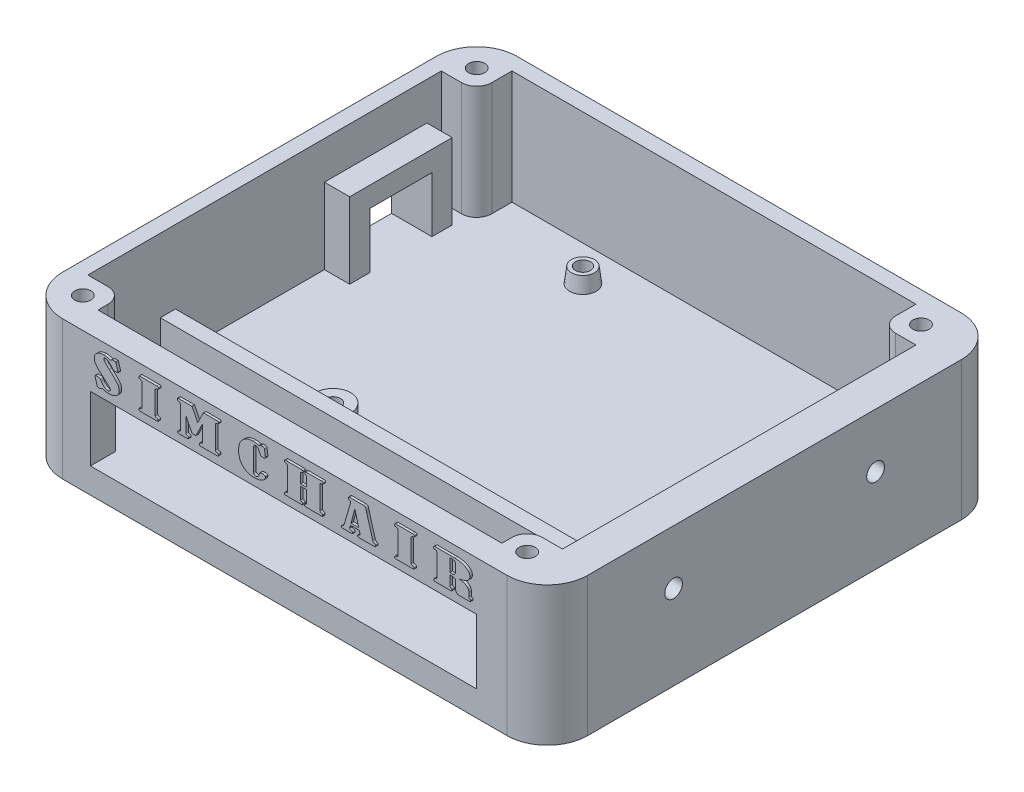
SolidWorks part; units mm, degrees
ref_plane "Спереди" through (0, 0, 0) normal (0, 0, 1) x (1, 0, 0)
ref_plane "Сверху" through (0, 0, 0) normal (0, 1, 0) x (1, 0, 0)
ref_plane "Справа" through (0, 0, 0) normal (1, 0, 0) x (0, 0, -1)
sketch "Sketch1" plane through (0, 0, 0) normal (0, 1, 0) x (1, 0, 0)
  line L1 (50, 45) -> (-50, 45)
  line L2 (50, 45) -> (50, -45)
  line L3 (50, -45) -> (-50, -45)
  line L4 (-50, 45) -> (-50, -45)
  line L5 (50, 45) -> (-50, -45) construction
  line L6 (50, -45) -> (-50, 45) construction
  point P0 (0, 0)
  dimension "D1" = 100
  dimension "D2" = 90
extrude "Boss-Extrude1" add sketch "Sketch1" along normal blind 5
sketch "Sketch2" plane through (0, 5, 0) normal (0, 1, 0) x (1, 0, 0)
  line L1 (-50, 45) -> (50, 45)
  line L2 (-50, 45) -> (-50, -45)
  line L3 (-50, -45) -> (50, -45)
  line L4 (50, 45) -> (50, -45)
  line L5 (-50, 45) -> (50, -45) construction
  line L6 (-50, -45) -> (50, 45) construction
  line L7 (-47, 42) -> (47, 42)
  line L8 (-47, 42) -> (-47, -42)
  line L9 (-47, -42) -> (47, -42)
  line L10 (47, 42) -> (47, -42)
  line L11 (-47, 42) -> (47, -42) construction
  line L12 (-47, -42) -> (47, 42) construction
  point P0 (0, 0)
  point P7 (0, 0)
  dimension "D1" = 3
  dimension "D2" = 3
  dimension "D3" = 94
  dimension "D4" = 84
  dimension "D5" = 100
  dimension "D6" = 90
extrude "Boss-Extrude2" add sketch "Sketch2" along normal blind 22.5
sketch "Эскиз1" plane through (0, 5, 0) normal (0, 1, 0) x (1, 0, 0)
  line L0 (-34.3, 37.65) -> (34.3, 37.65) construction
  line L1 (34.3, -15.65) -> (-34.3, 37.65) construction
  line L2 (-34.3, -15.65) -> (34.3, 37.65) construction
  line L3 (0, 42) -> (0, -42) construction
  line L4 (-47, -42) -> (47, -42) construction
  line L5 (31.8, -13.15) -> (-34.3, -13.15) construction
  line L6 (47, 42) -> (-47, 42) construction
  line L7 (34.3, 37.65) -> (34.3, -15.65) construction
  line L8 (34.3, -15.65) -> (-34.3, -15.65) construction
  line L9 (-34.3, -15.65) -> (-34.3, 37.65) construction
  line L10 (-34.3, 37.65) -> (-20.3, 37.65) construction
  line L11 (31.8, 37.65) -> (31.8, 19.85) construction
  line L12 (31.8, 19.85) -> (31.8, 35.05) construction
  line L13 (-20.3, 37.65) -> (-19, 37.65) construction
  line L14 (-20.3, 37.65) -> (-20.3, -15.65) construction
  line L15 (-19, 37.65) -> (31.8, 37.65) construction
  line L16 (31.8, 37.65) -> (31.8, -15.65) construction
  line L17 (31.8, -15.65) -> (31.8, -13.15) construction
  line L18 (31.8, 35.05) -> (-19, 35.05) construction
  line L19 (-19, 37.65) -> (-19, -15.65) construction
  circle A0 centre (31.8, -8.05) radius 1.5
  circle A1 centre (-20.3, -13.15) radius 1.5
  circle A2 centre (31.8, 19.85) radius 1.5
  circle A3 centre (-19, 35.05) radius 1.5
  circle A4 centre (-20.3, -13.15) radius 3.5
  circle A5 centre (-19, 35.05) radius 3.5
  circle A6 centre (31.8, 19.85) radius 3.5
  circle A7 centre (31.8, -8.05) radius 3.5
  point P3 (0, 11)
  point P11 (-20.3, -13.15)
  point P34 (0, 0)
  dimension "D12" = 3
  dimension "D2" = 7
  dimension "D3" = 53.3
  dimension "D4" = 68.6
  dimension "D5" = 14
  dimension "D6" = 1.3
  dimension "D7" = 50.8
  dimension "D8" = 2.5
  dimension "D9" = 5.1
  dimension "D10" = 27.9
  dimension "D11" = 15.2
  dimension "D13" = 31
extrude "Boss-Extrude3" add sketch "Эскиз1" along normal blind 3
sketch "Sketch7" plane through (0, 0, 0) normal (0, -1, 0) x (1, 0, 0)
  line L0 (-50, -45) -> (-50, 45) construction
  line L1 (-44, 39) -> (44, -39) construction
  line L2 (44, -39) -> (-44, -39) construction
  line L3 (-44, -39) -> (-44, 39) construction
  line L4 (-44, 39) -> (44, 39) construction
  line L5 (44, 39) -> (44, -39) construction
  line L6 (-50, 45) -> (50, 45) construction
  line L8 (50, 45) -> (50, -45) construction
  line L9 (50, -45) -> (-50, -45) construction
  circle A0 centre (44, -39) radius 1.6
  circle A1 centre (-44, -39) radius 1.6
  circle A2 centre (-44, 39) radius 1.6
  circle A3 centre (44, 39) radius 1.6
  dimension "D2" = 3.2
  dimension "D3" = 6
  dimension "D1" = 6
  dimension "D4" = 6
  dimension "D5" = 6
extrude "Cut-Extrude3" cut sketch "Sketch7" against normal through all
sketch "Sketch8" plane through (0, 0, 0) normal (0, -1, 0) x (1, 0, 0)
  line L0 (-50, 45) -> (50, 45) construction
  line L1 (42.375, 36.1854) -> (45.625, 36.1854)
  line L2 (45.625, 36.1854) -> (47.25, 39)
  line L3 (47.25, 39) -> (45.625, 41.8146)
  line L4 (45.625, 41.8146) -> (42.375, 41.8146)
  line L5 (42.375, 41.8146) -> (40.75, 39)
  line L6 (40.75, 39) -> (42.375, 36.1854)
  line L7 (42.375, -36.1854) -> (40.75, -39)
  line L8 (40.75, -39) -> (42.375, -41.8146)
  line L9 (42.375, -41.8146) -> (45.625, -41.8146)
  line L10 (45.625, -41.8146) -> (47.25, -39)
  line L11 (47.25, -39) -> (45.625, -36.1854)
  line L12 (45.625, -36.1854) -> (42.375, -36.1854)
  line L13 (-45.625, -36.1854) -> (-47.25, -39)
  line L14 (-47.25, -39) -> (-45.625, -41.8146)
  line L15 (-45.625, -41.8146) -> (-42.375, -41.8146)
  line L16 (-42.375, -41.8146) -> (-40.75, -39)
  line L17 (-40.75, -39) -> (-42.375, -36.1854)
  line L18 (-42.375, -36.1854) -> (-45.625, -36.1854)
  line L19 (-45.625, 36.1854) -> (-42.375, 36.1854)
  line L20 (-42.375, 36.1854) -> (-40.75, 39)
  line L21 (-40.75, 39) -> (-42.375, 41.8146)
  line L22 (-42.375, 41.8146) -> (-45.625, 41.8146)
  line L23 (-45.625, 41.8146) -> (-47.25, 39)
  line L24 (-47.25, 39) -> (-45.625, 36.1854)
  line L25 (50, -45) -> (-50, -45) construction
  circle A0 centre (44, 39) radius 3.25 construction
  circle A1 centre (44, -39) radius 3.25 construction
  circle A2 centre (-44, -39) radius 3.25 construction
  circle A3 centre (-44, 39) radius 3.25 construction
  dimension "D1" = 6.5
extrude "Cut-Extrude4" cut sketch "Sketch8" against normal blind 4
chamfer "Chamfer1" distance 10 angle 7 1 edges at (-19, 8, -31.55) first distance on face at (-19, 8, -31.55)
sketch "Sketch11" plane through (0, 5, 0) normal (0, 1, 0) x (1, 0, 0)
  circle A0 centre (-20.3, -13.15) radius 1.5
  circle A1 centre (-19, 35.05) radius 1.5
  circle A2 centre (31.8, -8.05) radius 1.5
  circle A3 centre (31.8, 19.85) radius 1.5
  circle A4 centre (31.8, 19.85) radius 1.5 construction
extrude "Cut-Extrude5" cut sketch "Sketch11" against normal through all
sketch "Sketch12" plane through (0, 0, 45) normal (0, 0, 1) x (1, 0, 0)
  line L0 (-50, 11.4) -> (50, 11.4) construction
  line L1 (-50, 27.5) -> (-50, 0) construction
  line L2 (50, 27.5) -> (50, 0) construction
  line L3 (-47, 5) -> (47, 5) construction
  line L4 (40, 17.8) -> (-21.2, 17.8)
  line L5 (40, 17.8) -> (40, 5)
  line L6 (40, 5) -> (-21.2, 5)
  line L7 (-21.2, 17.8) -> (-21.2, 5)
  line L8 (40, 17.8) -> (-21.2, 5) construction
  line L9 (40, 5) -> (-21.2, 17.8) construction
  point P6 (9.4, 11.4)
  point P15 (0, 11.4)
  dimension "D1" = 12.8
  dimension "D2" = 61.2
  dimension "D3" = 9.4
extrude "Cut-Extrude6" cut sketch "Sketch12" against normal up to surface (3 mm away) up to face at (0, 16.25, 42)
sketch "Sketch13" plane through (50, 0, 0) normal (1, 0, 0) x (0, 0, -1)
  line L0 (-45, 16.75) -> (45, 16.75) construction
  line L3 (-45, 27.5) -> (-45, 0) construction
  line L4 (45, 27.5) -> (45, 0) construction
  circle A0 centre (-20, 16.75) radius 1.75
  circle A1 centre (20, 16.75) radius 1.75
  point P10 (0, 16.75)
  point P11 (-45, 13.75)
  dimension "D1" = 40
  dimension "D4" = 3.5
  dimension "D2" = 20
  dimension "D3" = 3
extrude "Cut-Extrude7" cut sketch "Sketch13" against normal up to surface (3 mm away) up to face at (47, 16.25, 0)
sketch "Sketch14" plane through (50, 0, 0) normal (1, 0, 0) x (0, 0, -1)
  line L0 (-45, 13.75) -> (45, 13.75) construction
  line L1 (-45, 27.5) -> (-45, 0) construction
  line L2 (45, 27.5) -> (45, 0) construction
  line L4 (45, 0) -> (-45, 0)
  line L5 (45, 0) -> (45, 27.5)
  line L6 (45, 27.5) -> (-45, 27.5)
  line L7 (-45, 0) -> (-45, 27.5)
  line L8 (45, 0) -> (-45, 27.5) construction
  line L9 (45, 27.5) -> (-45, 0) construction
  circle A0 centre (-20, 16.75) radius 1.75
  circle A1 centre (20, 16.75) radius 1.75
  circle A2 centre (20, 16.75) radius 1.75 construction
  point P6 (0, 13.75)
extrude "Boss-Extrude7" add sketch "Sketch14" along normal blind 4
sketch "Sketch15" plane through (47, 0, 0) normal (-1, 0, 0) x (0, 0, 1)
  circle A0 centre (20, 16.75) radius 3.75
  circle A1 centre (-20, 16.75) radius 3.75
  dimension "D1" = 7.5
extrude "Cut-Extrude8" cut sketch "Sketch15" against normal blind 3
sketch "Sketch23" plane through (0, 5, 0) normal (0, 1, 0) x (1, 0, 0)
  line L2 (-40, -42) -> (-40, -35)
  line L3 (-47, -42) -> (-21.2, -42) construction
  line L4 (-47, 42) -> (-47, -42) construction
  line L5 (-47, -35) -> (-47, -42)
  line L6 (-40, -35) -> (-47, -35)
  line L7 (-40, -42) -> (-47, -42)
  line L8 (40, -42) -> (40, -35)
  line L9 (40, -42) -> (47, -42) construction
  line L10 (40, -35) -> (47, -35)
  line L11 (47, -42) -> (47, 42) construction
  line L12 (47, -35) -> (47, -42)
  line L13 (47, -42) -> (40, -42)
  line L14 (47, 35) -> (40, 35)
  line L15 (40, 35) -> (40, 42)
  line L16 (47, 42) -> (-47, 42) construction
  line L17 (40, 42) -> (47, 42)
  line L18 (47, 42) -> (47, 35)
  line L19 (-47, 42) -> (-47, -42) construction
  line L20 (-47, 35) -> (-40, 35)
  line L21 (-40, 35) -> (-40, 42)
  line L22 (-40, 42) -> (-47, 42)
  line L23 (-47, 42) -> (-47, 35)
  circle A0 centre (-44, 39) radius 1.6 construction
  circle A4 centre (-44, -39) radius 1.6
  circle A5 centre (-44, 39) radius 1.6
  circle A6 centre (44, 39) radius 1.6
  circle A7 centre (44, -39) radius 1.6
  circle A8 centre (-44, -39) radius 1.6 construction
  dimension "D1" = 7
extrude "Boss-Extrude13" add sketch "Sketch23" along normal up to surface (22.5 mm away) up to face at (2, 27.5, 0)
sketch "Sketch24" plane through (-47, 0, 0) normal (1, 0, 0) x (0, 0, -1)
  line L0 (35, 5) -> (-35, 5) construction
  line L1 (35, 27.5) -> (35, 5) construction
  line L5 (28.15, 5) -> (15.85, 5)
  line L6 (28.15, 5) -> (28.15, 16)
  line L7 (28.15, 16) -> (15.85, 16)
  line L8 (15.85, 5) -> (15.85, 16)
  line L9 (28.15, 5) -> (15.85, 16) construction
  line L10 (28.15, 16) -> (15.85, 5) construction
  point P6 (22, 10.5)
  dimension "D1" = 11
  dimension "D2" = 12.3
  dimension "D3" = 13
extrude "Cut-Extrude9" cut sketch "Sketch24" against normal through all
sketch "Sketch26" plane through (-47, 0, 0) normal (1, 0, 0) x (0, 0, -1)
  line L0 (15.85, 10.5) -> (28.15, 10.5) construction
  line L1 (15.85, 16) -> (15.85, 5) construction
  line L2 (28.15, 5) -> (28.15, 16) construction
  line L4 (28.15, 5) -> (15.85, 5)
  line L5 (28.15, 5) -> (28.15, 16)
  line L6 (28.15, 16) -> (15.85, 16)
  line L7 (15.85, 5) -> (15.85, 16)
  line L8 (28.15, 5) -> (15.85, 16) construction
  line L9 (28.15, 16) -> (15.85, 5) construction
  line L10 (32.15, 1) -> (11.85, 1)
  line L11 (32.15, 1) -> (32.15, 20)
  line L12 (32.15, 20) -> (11.85, 20)
  line L13 (11.85, 1) -> (11.85, 20)
  line L14 (32.15, 1) -> (11.85, 20) construction
  line L15 (32.15, 20) -> (11.85, 1) construction
  point P6 (22, 10.5)
  point P12 (22, 10.5)
  dimension "D1" = 4
  dimension "D2" = 4
extrude "Boss-Extrude15" add sketch "Sketch26" along normal blind 5
chamfer "Chamfer2" distance 0.3 angle 60 24 edges at (-41.5625, 0, 37.5927) (-41.5625, 0, 40.4073) (-44, 0, 41.8146) (-46.4375, 0, 40.4073) (-46.4375, 0, 37.5927) (-44, 0, 36.1854) (46.4375, 0, 37.5927) (44, 0, 36.1854) (41.5625, 0, 37.5927) (41.5625, 0, 40.4073) (44, 0, 41.8146) (46.4375, 0, 40.4073) (46.4375, 0, -40.4073) (44, 0, -41.8146) (41.5625, 0, -40.4073) (41.5625, 0, -37.5927) (44, 0, -36.1854) (46.4375, 0, -37.5927) (-46.4375, 0, -40.4073) (-44, 0, -41.8146) (-41.5625, 0, -40.4073) (-46.4375, 0, -37.5927) (-44, 0, -36.1854) (-41.5625, 0, -37.5927) first distance on face at (-19, 0, -33.55)
sketch "Sketch27" plane through (0, 0, 42) normal (0, 0, -1) x (-1, 0, 0)
  line L0 (21.2, 17.8) -> (36.5, 17.8)
  line L1 (36.5, 17.8) -> (36.5, 5)
  line L2 (40, 5) -> (21.2, 5) construction
  line L3 (36.5, 5) -> (21.2, 5)
  line L4 (21.2, 5) -> (21.2, 17.8)
  dimension "D1" = 15.3
extrude "Cut-Extrude10" cut sketch "Sketch27" against normal through all
fillet "Fillet4" radius 3 4 edges at (40, 16.25, 35) (-40, 16.25, 35) (40, 16.25, -35) (-40, 16.25, -35)
sketch "Sketch28" plane through (0, 5, 0) normal (0, 1, 0) x (1, 0, 0)
  line L0 (-47, -19.15) -> (47, -19.15) construction
  line L1 (-47, 11.85) -> (-47, -35) construction
  line L2 (47, -35) -> (47, 35) construction
  line L3 (-20.3, -13.15) -> (47, -13.15) construction
  line L4 (47, -20.65) -> (-47, -20.65)
  line L5 (47, -20.65) -> (47, -17.65)
  line L6 (47, -17.65) -> (-47, -17.65)
  line L7 (-47, -20.65) -> (-47, -17.65)
  line L8 (47, -20.65) -> (-47, -17.65) construction
  line L9 (47, -17.65) -> (-47, -20.65) construction
  point P6 (0, -19.15)
  dimension "D1" = 3
  dimension "D2" = 6
extrude "Boss-Extrude16" add sketch "Sketch28" along normal blind 8
fillet "Fillet5" radius 8 4 edges at (-50, 13.75, 45) (54, 13.75, -45) (-50, 13.75, -45) (54, 13.75, 45)
sketch "Sketch29" plane through (0, 0, 45) normal (0, 0, 1) x (1, 0, 0)
  line L0 (-42, 19.8) -> (46, 19.8) construction
  line L1 (-42, 27.5) -> (-42, 0) construction
  line L2 (46, 0) -> (46, 27.5) construction
  line L3 (40, 17.8) -> (-36.5, 17.8) construction
  text T0 "SIMCHAIR" font "Bernard MT Condensed" height 6
  dimension "D1" = 2
extrude "Boss-Extrude17" add sketch "Sketch29" along normal blind 0.5
sketch "Sketch30" plane through (0, 0, 42) normal (0, 0, -1) x (-1, 0, 0)
  line L0 (40, 27.5) -> (40, 5)
  line L1 (40, 5) -> (36.5, 5)
  line L2 (36.5, 5) -> (36.5, 17.8)
  line L3 (36.5, 17.8) -> (-40, 17.8)
  line L4 (-40, 17.8) -> (-40, 27.5)
  line L5 (-40, 27.5) -> (40, 27.5)
extrude "Boss-Extrude18" add sketch "Sketch30" along normal blind 2
